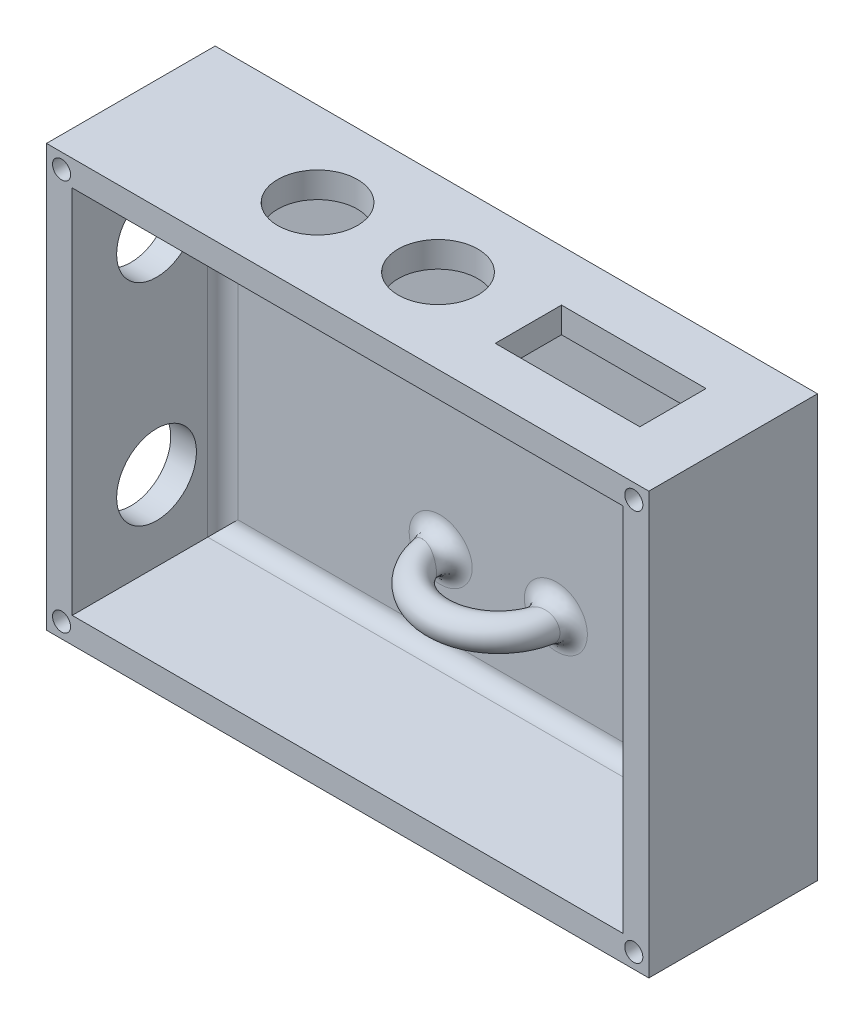
SolidWorks part; units mm, degrees
ref_plane "Front Plane" through (0, 0, 0) normal (0, 0, 1) x (1, 0, 0)
ref_plane "Top Plane" through (0, 0, 0) normal (0, 1, 0) x (1, 0, 0)
ref_plane "Right Plane" through (0, 0, 0) normal (1, 0, 0) x (0, 0, -1)
sketch "Sketch1" plane through (0, 0, 0) normal (0, 0, 1) x (1, 0, 0)
  line L0 (97.5, 2.5) -> (100, 2.5) construction
  line L1 (4.2678, 4.2678) -> (95.7322, 4.2678)
  line L2 (4.2678, 4.2678) -> (4.2678, 65.7322)
  line L3 (4.2678, 65.7322) -> (95.7322, 65.7322)
  line L4 (95.7322, 4.2678) -> (95.7322, 65.7322)
  line L5 (97.5, 2.5) -> (97.5, 0) construction
  line L6 (2.5, 2.5) -> (2.5, 0) construction
  line L7 (2.5, 2.5) -> (0, 2.5) construction
  line L8 (50, 65.7322) -> (50, 70) construction
  line L9 (0, 0) -> (100, 0)
  line L10 (0, 0) -> (0, 70)
  line L11 (0, 70) -> (100, 70)
  line L12 (100, 0) -> (100, 70)
  line L13 (4.2678, 35) -> (0, 35) construction
  line L14 (50, 4.2678) -> (50, 0) construction
  line L15 (95.7322, 35) -> (100, 35) construction
  line L16 (2.5, 67.5) -> (0, 67.5) construction
  line L17 (2.5, 67.5) -> (2.5, 70) construction
  line L18 (97.5, 67.5) -> (100, 67.5) construction
  line L19 (97.5, 67.5) -> (97.5, 70) construction
  line L20 (95.7322, 4.2678) -> (100, 0) construction
  line L21 (7.5, 35) -> (4.2678, 35) construction
  circle A0 centre (2.5, 2.5) radius 1.5
  circle A1 centre (2.5, 67.5) radius 1.5
  circle A2 centre (97.5, 67.5) radius 1.5
  circle A3 centre (97.5, 2.5) radius 1.5
  point P4 (96.4393, 3.5607)
  point P25 (99, 2.5)
  dimension "D16" = 3
  dimension "D2" = 70
  dimension "D3" = 2.5
  dimension "D4" = 1
  dimension "D11" = 100
extrude "Boss-Extrude1" add sketch "Sketch1" against normal blind 3 contours L1 L4 L3 L2 | L9 L12 L11 L10 A3 A2 A1 A0 L4 L1 L2 L3 region at (50, 35, 0) region at (1.2207, 35, 0)
extrude "Boss-Extrude2" add sketch "Sketch1<25>" along normal blind 25
sketch "Sketch1<25>" plane through (0, 0, 0) normal (0, 0, 1) x (1, 0, 0) same geometry as "Sketch1"
sketch "Sketch3" plane through (0, 0, 0) normal (-1, 0, 0) x (0, 0, 1)
  line L0 (-3, 70) -> (25, 0) construction
  line L3 (25, 70) -> (-3, 0) construction
  line L4 (11, 0) -> (11, 35) construction
  line L5 (-3, 0) -> (25, 0) construction
  line L6 (11, 35) -> (11, 70) construction
  line L7 (-3, 70) -> (25, 70) construction
  circle A0 centre (11, 52.5) radius 6.625
  circle A1 centre (11, 17.5) radius 6.625
  dimension "D1" = 13.25
  dimension "D2" = 13.25
extrude "Cut-Extrude1" cut sketch "Sketch3" against normal up to surface (4.2678 mm away) up to face at (4.2678, 35, 12.5)
sketch "Sketch4" plane through (0, 70, 0) normal (0, 1, 0) x (1, 0, 0)
  line L0 (0, -11) -> (100, -11) construction
  line L1 (0, 3) -> (0, -25) construction
  line L2 (100, 3) -> (100, -25) construction
  line L4 (90, -5.5) -> (66, -5.5)
  line L5 (90, -5.5) -> (90, -16.5)
  line L6 (90, -16.5) -> (66, -16.5)
  line L7 (66, -5.5) -> (66, -16.5)
  circle A0 centre (31, -11) radius 6.625
  circle A1 centre (51, -11) radius 6.625
  point P14 (66, -11)
  point P15 (90, -11)
  dimension "D1" = 13.25
  dimension "D4" = 11
  dimension "D2" = 15
  dimension "D3" = 20
  dimension "D5" = 24
  dimension "D6" = 10
extrude "Cut-Extrude2" cut sketch "Sketch4" against normal up to surface (4.2678 mm away) up to face at (50, 65.7322, 12.5)
sketch "Sketch5" plane through (0, 0, 0) normal (0, 0, 1) x (1, 0, 0)
  line L0 (50, 4.2678) -> (50, 65.7322) construction
  line L1 (4.2678, 4.2678) -> (95.7322, 4.2678) construction
  circle A0 centre (60, 19.2678) radius 2.5
  dimension "D3" = 5
  dimension "D1" = 10
  dimension "D2" = 15
revolve "Revolve1" add sketch "Sketch5" angle 180 about L0 region at (60, 19.2678, 0) reverse direction yes
fillet "Fillet1" radius 2.5 6 edges at (37.5, 19.2678, 0) (62.5, 19.2678, 0) (4.2678, 35, 0) (50, 65.7322, 0) (95.7322, 35, 0) (50, 4.2678, 0)
